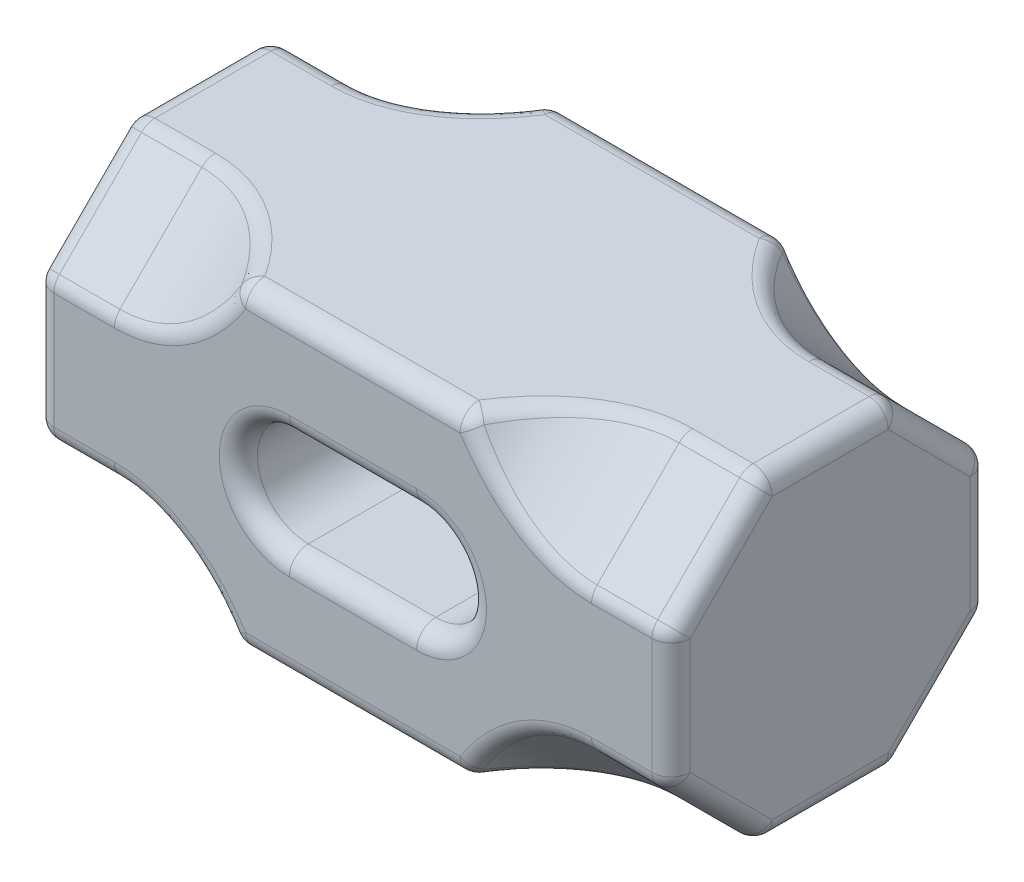
SolidWorks part; units mm, degrees
ref_plane "Front Plane" through (0, 0, 0) normal (0, 0, 1) x (1, 0, 0)
ref_plane "Top Plane" through (0, 0, 0) normal (0, 1, 0) x (1, 0, 0)
ref_plane "Right Plane" through (0, 0, 0) normal (1, 0, 0) x (0, 0, -1)
sketch "Sketch1" plane through (0, 0, 0) normal (1, 0, 0) x (0, 0, -1)
  line L1 (-25, -25) -> (25, -25)
  line L2 (-25, -25) -> (-25, 25)
  line L3 (-25, 25) -> (25, 25)
  line L4 (25, -25) -> (25, 25)
  line L5 (-25, -25) -> (25, 25) construction
  line L6 (-25, 25) -> (25, -25) construction
  point P0 (0, 0)
  dimension "D1" = 50
  dimension "D2" = 50
extrude "Boss-Extrude1" add sketch "Sketch1" along normal mid plane 100
sketch "Sketch8" plane through (0, 0, 0) normal (0, 0, 1) x (1, 0, 0)
  line L0 (-10, 0) -> (10, 0) construction
  line L1 (-10, 8) -> (10, 8)
  line L2 (-10, -8) -> (10, -8)
  arc A0 (-10, 8) -> (-10, -8) centre (-10, 0) ccw
  arc A1 (10, -8) -> (10, 8) centre (10, 0) ccw
  point P3 (0, 0)
  point P8 (3.114, 0)
  point P9 (0, 0)
  dimension "D2" = 8
  dimension "D1" = 20
extrude "Cut-Extrude3" cut sketch "Sketch8" against normal through all both and the other way through all
ref_plane "Plane2" through (0, 0, 0) normal (0, -0.7071, 0.7071) x (1, 0, 0)
sketch "Sketch9" plane through (0, 0, 0) normal (0, -0.7071, 0.7071) x (1, 0, 0)
  line L0 (50, 25) -> (37.5, 25)
  line L1 (50, 35.3553) -> (50, 0) construction
  line L2 (50, 35.3553) -> (-50, 35.3553) construction
  line L3 (50, 0) -> (-50, 0) construction
  line L4 (0, 0) -> (0, 35.3553) construction
  line L5 (0, 0) -> (50, 0) construction
  line L6 (17.2384, 35.3553) -> (50, 35.3553)
  line L7 (50, 35.3553) -> (50, 25)
  line L8 (-50, 35.3553) -> (-50, 25)
  line L9 (-17.2384, 35.3553) -> (-50, 35.3553)
  line L10 (-50, 25) -> (-37.5, 25)
  line L11 (-50, -25) -> (-37.5, -25)
  line L12 (-17.2384, -35.3553) -> (-50, -35.3553)
  line L13 (-50, -35.3553) -> (-50, -25)
  line L14 (50, -35.3553) -> (50, -25)
  line L15 (17.2384, -35.3553) -> (50, -35.3553)
  line L16 (50, -25) -> (37.5, -25)
  arc A0 (37.5, 25) -> (17.2384, 35.3553) centre (37.5, 50) cw
  arc A1 (-37.5, 25) -> (-17.2384, 35.3553) centre (-37.5, 50) ccw
  arc A2 (-37.5, -25) -> (-17.2384, -35.3553) centre (-37.5, -50) cw
  arc A3 (37.5, -25) -> (17.2384, -35.3553) centre (37.5, -50) ccw
  dimension "D1" = 25
  dimension "D2" = 12.5
  dimension "D3" = 25
extrude "Cut-Extrude4" cut sketch "Sketch9" against normal through all both and the other way through all
pattern_circular "CirPattern1" count 4 over 360 about axis through (-50, 0, 0) along (-1, 0, 0) of "Cut-Extrude4"
fillet "Fillet1" radius 3 60 edges at (-26.1228, 25, -14.2287) (-43.75, 25, -10.3553) (43.75, 25, -10.3553) (26.1228, 25, -14.2287) (-26.1228, -25, 14.2287) (-43.75, -25, 10.3553) (43.75, -25, 10.3553) (26.1228, -25, 14.2287) (-26.1228, 14.2287, 25) (-43.75, 10.3553, 25) (43.75, 10.3553, 25) (26.1228, 14.2287, 25) (26.1228, -25, -14.2287) (43.75, -25, -10.3553) (-26.1228, -25, -14.2287) (-43.75, -25, -10.3553) (0, 25, -25) (0, 25, 25) (0, -25, 25) (0, -25, -25) (50, -25, 0) (50, 0, 25) (50, 25, 0) (50, 0, -25) (-50, -25, 0) (-50, 0, 25) (-50, 25, 0) (-50, 0, -25) (0, 8, -25) (18, 0, -25) (0, -8, -25) (-18, 0, -25) (0, 8, 25) (18, 0, 25) (0, -8, 25) (-18, 0, 25) (-26.1228, 25, 14.2287) (-43.75, 25, 10.3553) (43.75, 25, 10.3553) (26.1228, 25, 14.2287) (26.1228, -14.2287, -25) (43.75, -10.3553, -25) (-26.1228, -14.2287, -25) (-43.75, -10.3553, -25) (50, 17.6777, 17.6777) (-50, 17.6777, 17.6777) (-50, -17.6777, -17.6777) (50, -17.6777, -17.6777) (-26.1228, 14.2287, -25) (-43.75, 10.3553, -25) (43.75, 10.3553, -25) (26.1228, 14.2287, -25) (-26.1228, -14.2287, 25) (-43.75, -10.3553, 25) (43.75, -10.3553, 25) (26.1228, -14.2287, 25) (50, 17.6777, -17.6777) (-50, 17.6777, -17.6777) (-50, -17.6777, 17.6777) (50, -17.6777, 17.6777)
